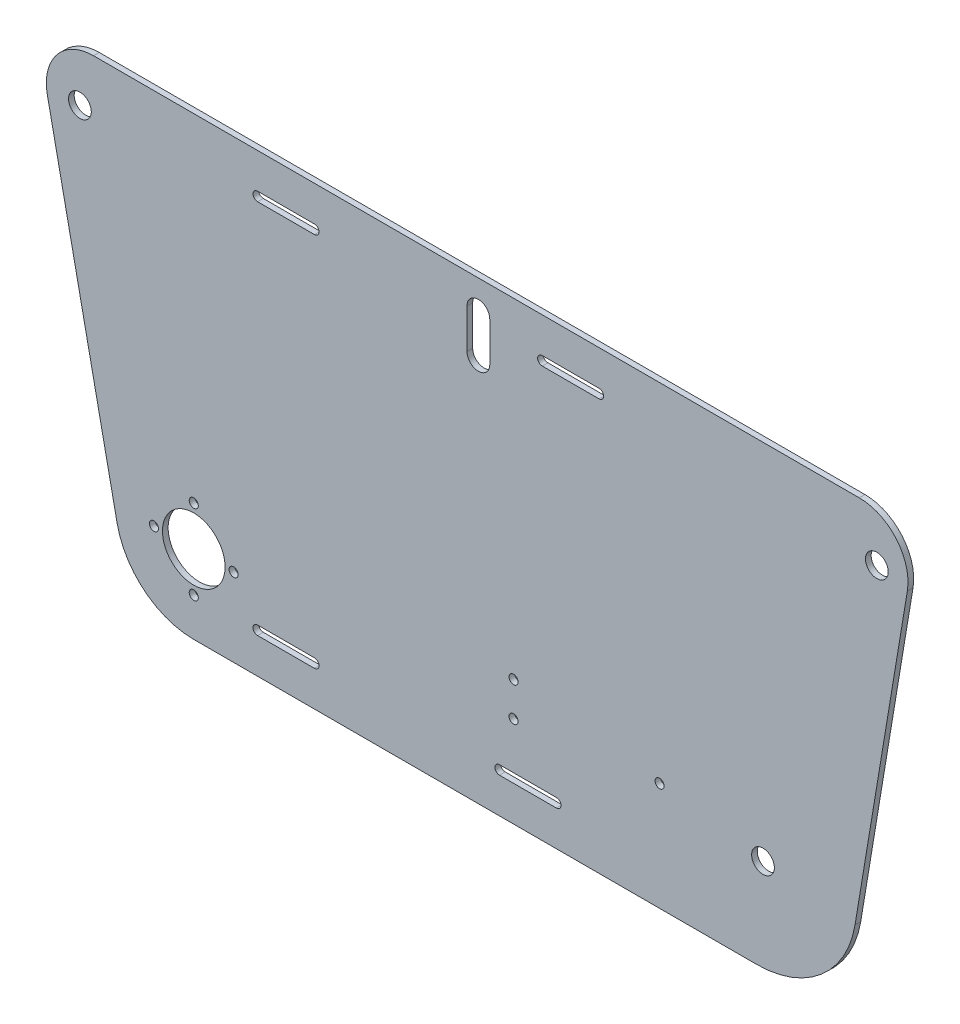
SolidWorks part; units mm, degrees
ref_plane "Front Plane" through (0, 0, 0) normal (0, 0, 1) x (1, 0, 0)
ref_plane "Top Plane" through (0, 0, 0) normal (0, 1, 0) x (1, 0, 0)
ref_plane "Right Plane" through (0, 0, 0) normal (1, 0, 0) x (0, 0, -1)
sketch "Sketch1" plane through (0, 0, 0) normal (0, 0, 1) x (1, 0, 0)
  line L1 (0, 0) -> (0, 115.062) construction
  line L2 (-140, 115.062) -> (140, 115.062) construction
  line L3 (-100, -37.4683) -> (100, -37.4683)
  line L4 (142.2945, 0.8576) -> (153.4347, 113.7361)
  line L5 (137.3964, 128.3085) -> (2.6036, 101.8154)
  line L6 (-2.6036, 101.8154) -> (-137.3964, 128.3085)
  line L7 (-153.3748, 113.2277) -> (-137.1523, -5.0634)
  line L8 (100, -34.9683) -> (-100, -34.9683) construction
  arc A12 (-137.1523, -5.0634) -> (-100, -37.4683) centre (-100, 0.0317) ccw
  arc A13 (100, -37.4683) -> (142.2945, 0.8576) centre (100, 5.0317) ccw
  arc A14 (153.4347, 113.7361) -> (137.3964, 128.3085) centre (140, 115.062) ccw
  arc A15 (2.6036, 101.8154) -> (-2.6036, 101.8154) centre (0, 115.062) cw
  arc A16 (-137.3964, 128.3085) -> (-153.3748, 113.2277) centre (-140, 115.062) ccw
  point P2 (0, 0)
  point P8 (0, 115.062)
  point P26 (0, -34.9683)
  circle B0 centre (-100, 0.0317) radius 35
  circle B1 centre (100, 5.0317) radius 40
  circle B2 centre (-140, 115.062) radius 11
  circle B3 centre (0, 115.062) radius 11
  circle B4 centre (140, 115.062) radius 11
  dimension "D1" = 200
  dimension "D3" = 280
  dimension "D7" = 279.5095
  dimension "D8" = 165.7768
sketch_block_instance "Block2-1"
sketch_block "Block2" parameters "D1"=52.784
sketch_block_instance "Block3-1"
sketch_block "Block3" parameters "D1"=49.6633
sketch_block_instance "Block4-1"
sketch_block "Block4"
sketch_block_instance "Block5-1"
sketch_block "Block5" parameters "D1"=22
sketch_block_instance "Block6-1"
sketch_block "Block6"
other "Belt1"
sketch "Sketch5" plane through (0, 0, 0) normal (0, 0, 1) x (1, 0, 0)
  line L12 (-100, -37.4683) -> (100, -37.4683) construction
  line L25 (110.1118, -2.4683) -> (77.5737, -2.4683)
  line L26 (65.3235, -2.4683) -> (34.5589, -2.4683)
  line L27 (134.4186, -22.4683) -> (143.6762, -22.4683)
  line L28 (143.4347, -2.4683) -> (134.6111, -2.4683)
  line L29 (143.4347, -2.4683) -> (143.4347, -22.4683)
  line L30 (16.6763, -22.4683) -> (134.2763, -22.4683)
  line L31 (15.513, -2.4683) -> (7.5179, -2.4683)
  line L32 (15.513, -22.4683) -> (7.5179, -22.4683)
  line L33 (7.5179, -2.4683) -> (7.5179, -22.4683)
  line L57 (14.6295, 0.5317) -> (66.6561, 0.5317)
  line L58 (66.6561, 0.5317) -> (66.6561, 7.0446)
  line L59 (66.6561, 14.0189) -> (66.6561, 20.5317)
  line L60 (66.6561, 20.5317) -> (14.6295, 20.5317)
  line L61 (10.0864, 20.5317) -> (8.6561, 20.5317)
  line L62 (8.6561, 20.5317) -> (8.6561, 19.2625)
  line L63 (8.6561, 13.801) -> (8.6561, 7.2625)
  line L64 (8.6561, 1.801) -> (8.6561, 0.5317)
  line L65 (8.6561, 0.5317) -> (10.0864, 0.5317)
  circle A0 centre (100, 5.0317) radius 11
  circle A2 centre (100, 5.0317) radius 7
  circle A29 centre (63.6561, 10.5317) radius 1.6
  circle A30 centre (12.3579, 16.5317) radius 1.6
  arc A36 (66.6561, 7.0446) -> (66.6561, 14.0189) centre (63.6561, 10.5317) ccw
  arc A37 (14.6295, 20.5317) -> (10.0864, 20.5317) centre (12.3579, 16.5317) ccw
  arc A38 (8.6561, 19.2625) -> (8.6561, 13.801) centre (12.3579, 16.5317) ccw
  arc A39 (8.6561, 7.2625) -> (8.6561, 1.801) centre (12.3579, 4.5317) ccw
  arc A40 (10.0864, 0.5317) -> (14.6295, 0.5317) centre (12.3579, 4.5317) ccw
  circle A41 centre (12.3579, 4.5317) radius 1.6
  dimension "D1" = 3.2
  dimension "D2" = 4.6
  dimension "D23" = 22
  dimension "D24" = 14
  dimension "D3" = 1.1383
  dimension "D4" = 2.5685
  dimension "D5" = 4.8401
  dimension "D6" = 136.1584
  dimension "D7" = 7.9951
  dimension "D8" = 9.1584
  dimension "D9" = 27.0411
  dimension "D10" = 56.1383
  dimension "D11" = 57.8057
  dimension "D12" = 59.1383
  dimension "D13" = 70.0559
  dimension "D14" = 102.594
  dimension "D15" = 126.7584
  dimension "D16" = 126.9007
  dimension "D17" = 127.0932
  dimension "D18" = 135.9169
  dimension "D19" = 20
  dimension "D20" = 23
  dimension "D21" = 29.5129
  dimension "D22" = 15
  dimension "D25" = 10
sketch "Sketch3" plane through (0, 0, 0) normal (0, 0, 1) x (1, 0, 0)
  line L0 (-100, -27.4683) -> (97.7714, -27.4683)
  line L1 (-100, -37.4683) -> (100, -37.4683) construction
  line L2 (-126.9257, -5.5588) -> (-151.4564, 112.5875)
  line L3 (132.3429, 1.8398) -> (150.7181, 112.5875)
  line L4 (-137.1523, -5.0634) -> (-126.9257, -5.5588) construction
  line L6 (142.2945, 0.8576) -> (132.3429, 1.8398) construction
  line L7 (142.2945, 0.8576) -> (153.4347, 113.7361) construction
  line L8 (-135.2278, 132.5317) -> (133.8103, 132.5317)
  line L9 (-4, 121.9902) -> (-4, 108.1338)
  line L10 (4, 121.9902) -> (4, 108.1338)
  circle A0 centre (-140, 115.062) radius 4
  circle A1 centre (0, 115.062) radius 4
  circle A2 centre (140, 115.062) radius 4
  circle A3 centre (100, 5.0317) radius 4
  circle A4 centre (-100, 0.0317) radius 11
  circle A6 centre (140, 115.062) radius 11 construction
  arc A7 (-100, -27.4683) -> (-126.9257, -5.5588) centre (-100, 0.0317) cw
  arc A8 (97.7714, -27.4683) -> (132.3429, 1.8398) centre (97.7714, 7.5758) ccw
  arc A10 (-151.4564, 112.5875) -> (-135.2278, 132.5317) centre (-135.2278, 115.9571) cw
  arc A11 (150.7181, 112.5875) -> (133.8103, 132.5317) centre (133.8103, 115.3929) ccw
  circle A13 centre (63.6561, 10.5317) radius 1.6 construction
  circle A14 centre (12.3579, 4.5317) radius 1.6 construction
  circle A15 centre (12.3579, 16.5317) radius 1.6 construction
  circle A16 centre (63.6561, 10.5317) radius 1.6
  circle A17 centre (12.3579, 4.5317) radius 1.6
  circle A18 centre (12.3579, 16.5317) radius 1.6
  circle A19 centre (-100, 0.0317) radius 14 construction
  circle A20 centre (-100, 14.0317) radius 1.6
  circle A21 centre (-86, 0.0317) radius 1.6
  circle A22 centre (-100, -13.9683) radius 1.6
  circle A23 centre (-114, 0.0317) radius 1.6
  circle A24 centre (0, 115.062) radius 8 construction
  arc A25 (-4, 121.9902) -> (4, 121.9902) centre (0, 121.9902) cw
  arc A26 (-4, 108.1338) -> (4, 108.1338) centre (0, 108.1338) ccw
  point P23 (-148.7843, 111.1761)
  point P24 (-127.245, -3.7047)
  point P29 (-127.0203, -5.0634)
  point P31 (-150.5316, 108.1338)
  point P32 (0, 0)
  dimension "D1" = 8
  dimension "D5" = 22
  dimension "D6" = 28
  dimension "D7" = 3.2
  dimension "D2" = 10
  dimension "D3" = 10
  dimension "D4" = 160
  dimension "D9" = 8
  dimension "D8" = 4
extrude "Boss-Extrude1" add sketch "Sketch3" along normal blind 2 contours A10 L2 A7 L0 A8 L3 A11 L8 A26 L9 A25 L10 A23 A22 A21 A20 A18 A17 A16 A4 A3 A2 A0 region at (1.4431, 55.8088, 0)
sketch "Sketch6" plane through (0, 0, 0) normal (0, 0, 1) x (1, 0, 0)
  line L0 (-77.58, -11.8683) -> (-57.58, -11.8683)
  line L1 (-77.58, -15.0683) -> (-57.58, -15.0683)
  line L2 (7.42, -11.8683) -> (27.42, -11.8683)
  line L3 (7.42, -15.0683) -> (27.42, -15.0683)
  line L4 (-100, -27.4683) -> (97.7714, -27.4683) construction
  line L5 (7.42, -13.4683) -> (-57.58, -13.4683) construction
  line L6 (-25.08, -27.4683) -> (-25.08, 132.5317) construction
  line L7 (-135.2278, 132.5317) -> (133.8103, 132.5317) construction
  line L8 (-25.08, 52.5317) -> (-5.468, 52.5317) construction
  line L9 (-77.58, 120.1317) -> (-57.58, 120.1317)
  line L10 (-77.58, 116.9317) -> (-57.58, 116.9317)
  line L11 (22.42, 120.1317) -> (42.42, 120.1317)
  line L12 (22.42, 116.9317) -> (42.42, 116.9317)
  arc A0 (-77.58, -11.8683) -> (-77.58, -15.0683) centre (-77.58, -13.4683) ccw
  arc A1 (-57.58, -11.8683) -> (-57.58, -15.0683) centre (-57.58, -13.4683) cw
  arc A2 (27.42, -11.8683) -> (27.42, -15.0683) centre (27.42, -13.4683) cw
  arc A3 (7.42, -11.8683) -> (7.42, -15.0683) centre (7.42, -13.4683) ccw
  arc A4 (-57.58, 116.9317) -> (-57.58, 120.1317) centre (-57.58, 118.5317) ccw
  arc A5 (-77.58, 116.9317) -> (-77.58, 120.1317) centre (-77.58, 118.5317) cw
  arc A6 (22.42, 116.9317) -> (22.42, 120.1317) centre (22.42, 118.5317) cw
  arc A7 (42.42, 116.9317) -> (42.42, 120.1317) centre (42.42, 118.5317) ccw
  point P6 (-67.58, -11.8683)
  dimension "D1" = 3.2
  dimension "D2" = 32.42
  dimension "D3" = 20
  dimension "D5" = 14
  dimension "D6" = 2
  dimension "D4" = 2
extrude "Cut-Extrude3" cut sketch "Sketch6" along normal through all
ref_plane "Plane1" through (0, 52.5317, 0) normal (0, -1, 0) x (-1, 0, 0)
